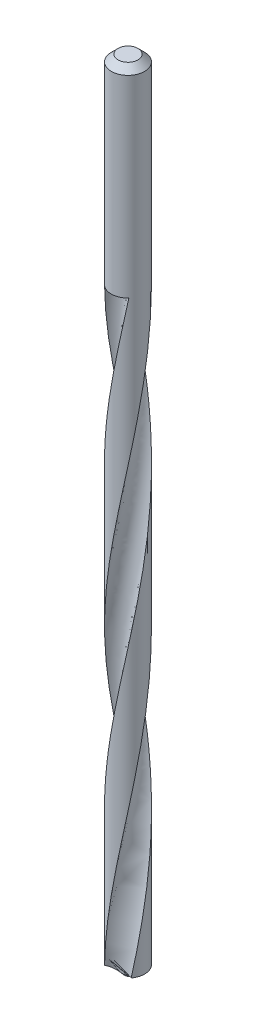
SolidWorks part; units mm, degrees
ref_plane "Front Plane" through (0, 0, 0) normal (0, 0, 1) x (1, 0, 0)
ref_plane "Top Plane" through (0, 0, 0) normal (0, 1, 0) x (1, 0, 0)
ref_plane "Right Plane" through (0, 0, 0) normal (1, 0, 0) x (0, 0, -1)
sketch "Sketch1" plane through (0, 0, 0) normal (0, 1, 0) x (1, 0, 0)
  circle A0 centre (0, 0) radius 2.5
  dimension "D1" = 5
extrude "Boss-Extrude1" add sketch "Sketch1" along normal blind 120
sketch "Sketch8" plane through (0, 0, 0) normal (0, -1, 0) x (1, 0, 0)
  circle A0 centre (0, 0) radius 2.5 construction
  circle A1 centre (0, 0) radius 2.5
curve "Helix/Spiral1" pitch 90 height 90 turns 1
sketch3d "3DSketch1"
  arc A0 (0, 90, 2.5) -> (-2.2408, 64.679, -1.178) centre (97.0474, 63.7776, 34.2202) ccw
  spline S0 degree 3 poles (901.1946, -156.9427, -401.491) (-49.4487, -123.776, -60.4385) (-8.2979, -57.0971, 8.5703) (1.8138, 11.25, 1.8138) (2.3698, 16.875, 0.9816) (2.5651, 22.5, 0) (2.3698, 28.125, -0.9816) (1.8138, 33.75, -1.8138) (0.9816, 39.375, -2.3698) (0, 45, -2.5651) (-0.9816, 50.625, -2.3698) (-1.8138, 56.25, -1.8138) (-2.3698, 61.875, -0.9816) (-2.5651, 67.5, 0) (-2.3698, 73.125, 0.9816) (-1.8138, 78.75, 1.8138) (8.2978, 147.0966, 8.5702) (49.4481, 213.7749, -60.4374) (-901.1717, 246.9419, -401.4828) knots -2.09082 -2.09082 -2.09082 -2.09082 0.0625 0.125 0.1875 0.25 0.3125 0.375 0.4375 0.5 0.5625 0.625 0.6875 0.75 0.8125 0.875 0.9375 3.090803 3.090803 3.090803 3.090803 only from (0, 0, 2.5) to (0, 90, 2.5) construction
  spline S1 degree 3 poles (0, 0, 2.5) (0.3272, 1.8746, 2.5) (0.9816, 5.6252, 2.3698) (1.8138, 11.25, 1.8138) (2.3698, 16.875, 0.9816) (2.5651, 22.5, 0) (2.3698, 28.125, -0.9816) (1.8138, 33.75, -1.8138) (0.9816, 39.375, -2.3698) (0, 45, -2.5651) (-0.9816, 50.625, -2.3698) (-1.8138, 56.25, -1.8138) (-2.3698, 61.875, -0.9816) (-2.5651, 67.5, 0) (-2.3698, 73.125, 0.9816) (-1.8138, 78.75, 1.8138) (-0.9816, 84.3748, 2.3698) (-0.3272, 88.1254, 2.5) (0, 90, 2.5) knots 0 0 0 0 0.0625 0.125 0.1875 0.25 0.3125 0.375 0.4375 0.5 0.5625 0.625 0.6875 0.75 0.8125 0.875 0.9375 1 1 1 1
  point P3 (132.3363, 74.9908, -64.476)
sketch "Sketch9" plane through (0, 0, 0) normal (0, 0, 1) x (1, 0, 0)
sketch "Sketch10" plane through (0, 0, 0) normal (0, -1, 0) x (-1, 0, 0)
  circle A0 centre (0, -2.5) radius 2
sweep "Cut-Sweep1" cut profiles "Sketch10" path "3DSketch1"
pattern_circular "CirPattern1" count 2 over 360 about axis through (0, 120, 0) along (0, -1, 0) of "Cut-Sweep1" reverse direction yes
sketch "Sketch12" plane through (0, 0, 0) normal (1, 0, 0) x (0, 0, -1)
  line L0 (0, 0) -> (0, 5) construction
  line L1 (0, 0) -> (-6.127, 3.5374)
  line L2 (-6.127, 3.5374) -> (-6.127, -3.5902)
  line L3 (-6.127, -3.5902) -> (0, -3.5902)
  line L4 (0, -3.5902) -> (0, 0)
  dimension "D1" = 5
  dimension "D2" = 60
revolve "Cut-Revolve1" cut sketch "Sketch12" angle 360 about L0
chamfer "Chamfer1" distance 1 angle 45 1 edges at (0, 120, 2.5)
